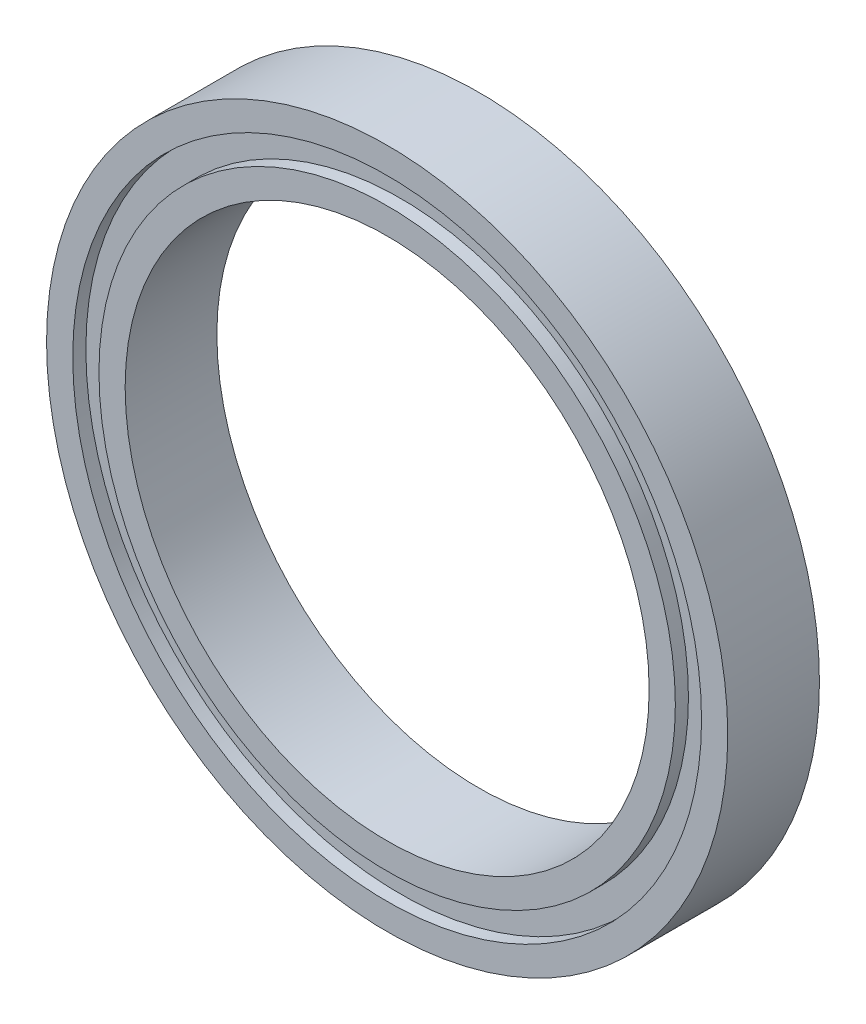
SolidWorks part; units mm, degrees
material "普通碳钢"
ref_plane "前视基准面" through (0, 0, 0) normal (0, 0, 1) x (1, 0, 0)
ref_plane "上视基准面" through (0, 0, 0) normal (0, 1, 0) x (1, 0, 0)
ref_plane "右视基准面" through (0, 0, 0) normal (1, 0, 0) x (0, 0, -1)
sketch "草图1" plane through (0, 0, 0) normal (0, 0, 1) x (1, 0, 0)
  circle A0 centre (0, 0) radius 20
  circle A1 centre (0, 0) radius 26
extrude "拉伸1" add sketch "草图1" along normal blind 3.5 and the other way blind 3.5
sketch "草图2" plane through (0, 0, 3.5) normal (0, 0, 1) x (1, 0, 0)
  circle A0 centre (0, 0) radius 22
  circle A1 centre (0, 0) radius 24
extrude "切除-拉伸1" cut sketch "草图2" against normal blind 1
mirror "镜向1" about plane through (0, 0, 0) normal (0, 0, 1) of "切除-拉伸1"
